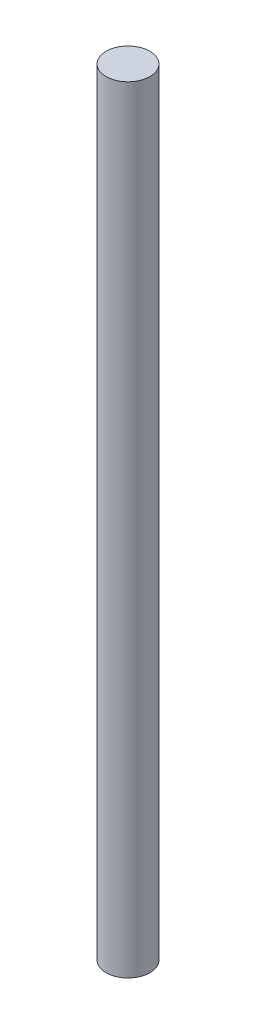
SolidWorks part; units mm, degrees
ref_plane "前视基准面" through (0, 0, 0) normal (0, 0, 1) x (1, 0, 0)
ref_plane "上视基准面" through (0, 0, 0) normal (0, 1, 0) x (1, 0, 0)
ref_plane "右视基准面" through (0, 0, 0) normal (1, 0, 0) x (0, 0, -1)
sketch "草图1" plane through (0, 0, 0) normal (0, 1, 0) x (1, 0, 0)
  circle A0 centre (0, 0) radius 1
  dimension "D1" = 2
extrude "凸台-拉伸1" add sketch "草图1" along normal blind 35.4
